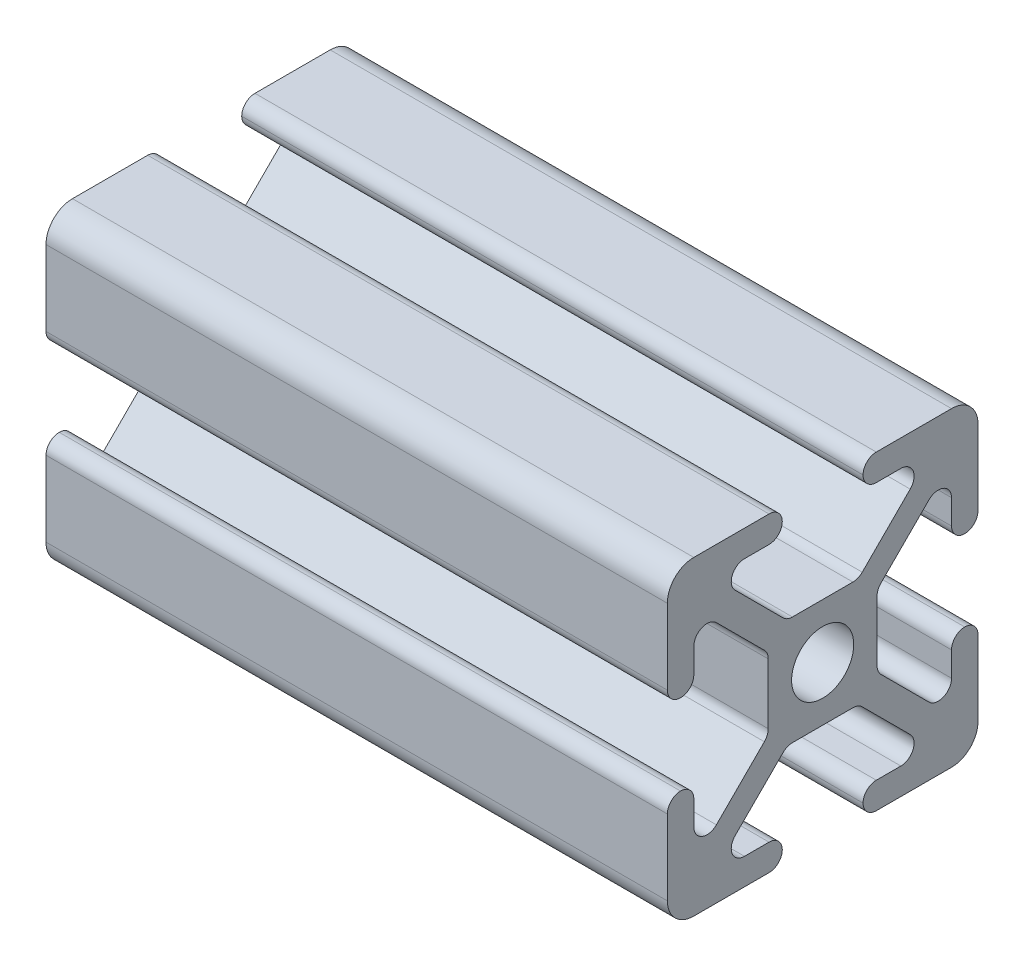
SolidWorks part; units mm, degrees
ref_plane "Front Plane" through (0, 0, 0) normal (1, 0, 0) x (0, 1, 0)
ref_plane "Top Plane" through (0, 0, 0) normal (0, 0, 1) x (0, 1, 0)
ref_plane "Right Plane" through (0, 0, 0) normal (0, 1, 0) x (-1, 0, 0)
sketch "Sketch1" plane through (0, 0, 0) normal (1, 0, 0) x (0, 1, 0)
  line L0 (0, 0) -> (0, 12.5) construction
  line L1 (-12.5, -12.5) -> (12.5, -12.5)
  line L2 (-12.5, -12.5) -> (-12.5, 12.5)
  line L3 (-12.5, 12.5) -> (12.5, 12.5)
  line L4 (12.5, -12.5) -> (12.5, 12.5)
  line L5 (-12.5, -12.5) -> (12.5, 12.5) construction
  line L6 (-12.5, 12.5) -> (12.5, -12.5) construction
  line L7 (-3.25, 12.5) -> (-3.25, 10.37)
  line L8 (-3.25, 10.37) -> (-8.8639, 10.37)
  line L9 (-8.8639, 10.37) -> (-2.8739, 4.38)
  line L10 (-2.8739, 4.38) -> (2.8739, 4.38)
  line L11 (8.8639, 10.37) -> (2.8739, 4.38)
  line L12 (3.25, 10.37) -> (8.8639, 10.37)
  line L13 (3.25, 12.5) -> (3.25, 10.37)
  line L14 (12.5, -3.25) -> (10.37, -3.25)
  line L15 (10.37, -3.25) -> (10.37, -8.8639)
  line L16 (10.37, -8.8639) -> (4.38, -2.8739)
  line L17 (4.38, 2.8739) -> (4.38, -2.8739)
  line L18 (10.37, 8.8639) -> (4.38, 2.8739)
  line L19 (10.37, 3.25) -> (10.37, 8.8639)
  line L20 (12.5, 3.25) -> (10.37, 3.25)
  line L21 (-3.25, -12.5) -> (-3.25, -10.37)
  line L22 (-3.25, -10.37) -> (-8.8639, -10.37)
  line L23 (-8.8639, -10.37) -> (-2.8739, -4.38)
  line L24 (2.8739, -4.38) -> (-2.8739, -4.38)
  line L25 (8.8639, -10.37) -> (2.8739, -4.38)
  line L26 (3.25, -10.37) -> (8.8639, -10.37)
  line L27 (3.25, -12.5) -> (3.25, -10.37)
  line L28 (-12.5, 3.25) -> (-10.37, 3.25)
  line L29 (-10.37, 3.25) -> (-10.37, 8.8639)
  line L30 (-10.37, 8.8639) -> (-4.38, 2.8739)
  line L31 (-4.38, -2.8739) -> (-4.38, 2.8739)
  line L32 (-10.37, -8.8639) -> (-4.38, -2.8739)
  line L33 (-10.37, -3.25) -> (-10.37, -8.8639)
  line L34 (-12.5, -3.25) -> (-10.37, -3.25)
  circle A0 centre (0, 0) radius 2.5
  point P0 (0, 0)
  point P15 (0, 4.38)
  dimension "D3" = 5
  dimension "D1" = 25
  dimension "D2" = 25
  dimension "D4" = 2.13
  dimension "D5" = 2.13
  dimension "D6" = 6.5
  dimension "D7" = 4.38
  dimension "D8" = 4
extrude "Boss-Extrude1" add sketch "Sketch1" along normal blind 50 contours L34 L2 L1 L21 L22 L23 L24 L25 L26 L27 L4 L14 L15 L16 L17 L18 L19 L20 L3 L13 L12 L11 L10 L9 L8 L7 L28 L29 L30 L31 L32 L33 A0 region at (0, -12.1464, -7.875)
fillet "Fillet1" radius 1.065 32 edges at (25, -10.37, -8.8639) (25, 2.8739, -4.38) (25, -2.8739, -4.38) (25, -4.38, 2.8739) (25, -4.38, -2.8739) (25, -2.8739, 4.38) (25, 2.8739, 4.38) (25, 4.38, 2.8739) (25, 4.38, -2.8739) (25, -8.8639, -10.37) (25, 8.8639, -10.37) (25, 10.37, -8.8639) (25, -10.37, 8.8639) (25, -8.8639, 10.37) (25, 10.37, 8.8639) (25, 8.8639, 10.37) (25, 12.5, 3.25) (25, -3.25, -12.5) (25, -10.37, 3.25) (25, 10.37, 3.25) (25, -10.37, -3.25) (25, -12.5, -3.25) (25, -12.5, 3.25) (25, 3.25, -10.37) (25, -3.25, -10.37) (25, 3.25, -12.5) (25, 10.37, -3.25) (25, 12.5, -3.25) (25, 3.25, 12.5) (25, 3.25, 10.37) (25, -3.25, 10.37) (25, -3.25, 12.5)
fillet "Fillet2" radius 2.13 4 edges at (25, 12.5, -12.5) (25, -12.5, -12.5) (25, 12.5, 12.5) (25, -12.5, 12.5)
sketch "Sketch2" plane through (50, 0, 0) normal (1, 0, 0) x (0, 1, 0)
  line L0 (10.37, -12.5) -> (4.315, -12.5)
  line L1 (10.37, -12.5) -> (4.315, -12.5)
  line L2 (4.315, -10.37) -> (6.2927, -10.37)
  line L3 (4.315, -10.37) -> (6.2927, -10.37)
  line L4 (7.0458, -8.5519) -> (3.1858, -4.6919)
  line L5 (7.0458, -8.5519) -> (3.1858, -4.6919)
  line L6 (2.4327, -4.38) -> (-2.4327, -4.38)
  line L7 (2.4327, -4.38) -> (-2.4327, -4.38)
  line L8 (-3.1858, -4.6919) -> (-7.0458, -8.5519)
  line L9 (-3.1858, -4.6919) -> (-7.0458, -8.5519)
  line L10 (-6.2927, -10.37) -> (-4.315, -10.37)
  line L11 (-6.2927, -10.37) -> (-4.315, -10.37)
  line L12 (-4.315, -12.5) -> (-10.37, -12.5)
  line L13 (-4.315, -12.5) -> (-10.37, -12.5)
  line L14 (-12.5, -10.37) -> (-12.5, -4.315)
  line L15 (-12.5, -10.37) -> (-12.5, -4.315)
  line L16 (-10.37, -4.315) -> (-10.37, -6.2927)
  line L17 (-10.37, -4.315) -> (-10.37, -6.2927)
  line L18 (-8.5519, -7.0458) -> (-4.6919, -3.1858)
  line L19 (-8.5519, -7.0458) -> (-4.6919, -3.1858)
  line L20 (-4.38, -2.4327) -> (-4.38, 2.4327)
  line L21 (-4.38, -2.4327) -> (-4.38, 2.4327)
  line L22 (-4.6919, 3.1858) -> (-8.5519, 7.0458)
  line L23 (-4.6919, 3.1858) -> (-8.5519, 7.0458)
  line L24 (-10.37, 6.2927) -> (-10.37, 4.315)
  line L25 (-10.37, 6.2927) -> (-10.37, 4.315)
  line L26 (-12.5, 4.315) -> (-12.5, 10.37)
  line L27 (-12.5, 4.315) -> (-12.5, 10.37)
  line L28 (-10.37, 12.5) -> (-4.315, 12.5)
  line L29 (-10.37, 12.5) -> (-4.315, 12.5)
  line L30 (-4.315, 10.37) -> (-6.2927, 10.37)
  line L31 (-4.315, 10.37) -> (-6.2927, 10.37)
  line L32 (-7.0458, 8.5519) -> (-3.1858, 4.6919)
  line L33 (-7.0458, 8.5519) -> (-3.1858, 4.6919)
  line L34 (-2.4327, 4.38) -> (2.4327, 4.38)
  line L35 (-2.4327, 4.38) -> (2.4327, 4.38)
  line L36 (3.1858, 4.6919) -> (7.0458, 8.5519)
  line L37 (3.1858, 4.6919) -> (7.0458, 8.5519)
  line L38 (6.2927, 10.37) -> (4.315, 10.37)
  line L39 (6.2927, 10.37) -> (4.315, 10.37)
  line L40 (4.315, 12.5) -> (10.37, 12.5)
  line L41 (4.315, 12.5) -> (10.37, 12.5)
  line L42 (12.5, 10.37) -> (12.5, 4.315)
  line L43 (12.5, 10.37) -> (12.5, 4.315)
  line L44 (10.37, 4.315) -> (10.37, 6.2927)
  line L45 (10.37, 4.315) -> (10.37, 6.2927)
  line L46 (8.5519, 7.0458) -> (4.6919, 3.1858)
  line L47 (8.5519, 7.0458) -> (4.6919, 3.1858)
  line L48 (4.38, 2.4327) -> (4.38, -2.4327)
  line L49 (4.38, 2.4327) -> (4.38, -2.4327)
  line L50 (4.6919, -3.1858) -> (8.5519, -7.0458)
  line L51 (4.6919, -3.1858) -> (8.5519, -7.0458)
  line L52 (10.37, -6.2927) -> (10.37, -4.315)
  line L53 (10.37, -6.2927) -> (10.37, -4.315)
  line L54 (12.5, -4.315) -> (12.5, -10.37)
  line L55 (12.5, -4.315) -> (12.5, -10.37)
  arc A0 (10.37, -12.5) -> (12.5, -10.37) centre (10.37, -10.37) ccw
  circle A1 centre (0, 0) radius 2.5
  circle A2 centre (0, 0) radius 2.5
  arc A3 (10.37, -12.5) -> (12.5, -10.37) centre (10.37, -10.37) ccw
  arc A4 (3.25, -11.435) -> (4.315, -12.5) centre (4.315, -11.435) ccw
  arc A5 (3.25, -11.435) -> (4.315, -12.5) centre (4.315, -11.435) ccw
  arc A6 (4.315, -10.37) -> (3.25, -11.435) centre (4.315, -11.435) ccw
  arc A7 (4.315, -10.37) -> (3.25, -11.435) centre (4.315, -11.435) ccw
  arc A8 (6.2927, -10.37) -> (7.0458, -8.5519) centre (6.2927, -9.305) ccw
  arc A9 (6.2927, -10.37) -> (7.0458, -8.5519) centre (6.2927, -9.305) ccw
  arc A10 (3.1858, -4.6919) -> (2.4327, -4.38) centre (2.4327, -5.445) ccw
  arc A11 (3.1858, -4.6919) -> (2.4327, -4.38) centre (2.4327, -5.445) ccw
  arc A12 (-2.4327, -4.38) -> (-3.1858, -4.6919) centre (-2.4327, -5.445) ccw
  arc A13 (-2.4327, -4.38) -> (-3.1858, -4.6919) centre (-2.4327, -5.445) ccw
  arc A14 (-7.0458, -8.5519) -> (-6.2927, -10.37) centre (-6.2927, -9.305) ccw
  arc A15 (-7.0458, -8.5519) -> (-6.2927, -10.37) centre (-6.2927, -9.305) ccw
  arc A16 (-3.25, -11.435) -> (-4.315, -10.37) centre (-4.315, -11.435) ccw
  arc A17 (-3.25, -11.435) -> (-4.315, -10.37) centre (-4.315, -11.435) ccw
  arc A18 (-4.315, -12.5) -> (-3.25, -11.435) centre (-4.315, -11.435) ccw
  arc A19 (-4.315, -12.5) -> (-3.25, -11.435) centre (-4.315, -11.435) ccw
  arc A20 (-12.5, -10.37) -> (-10.37, -12.5) centre (-10.37, -10.37) ccw
  arc A21 (-12.5, -10.37) -> (-10.37, -12.5) centre (-10.37, -10.37) ccw
  arc A22 (-11.435, -3.25) -> (-12.5, -4.315) centre (-11.435, -4.315) ccw
  arc A23 (-11.435, -3.25) -> (-12.5, -4.315) centre (-11.435, -4.315) ccw
  arc A24 (-10.37, -4.315) -> (-11.435, -3.25) centre (-11.435, -4.315) ccw
  arc A25 (-10.37, -4.315) -> (-11.435, -3.25) centre (-11.435, -4.315) ccw
  arc A26 (-10.37, -6.2927) -> (-8.5519, -7.0458) centre (-9.305, -6.2927) ccw
  arc A27 (-10.37, -6.2927) -> (-8.5519, -7.0458) centre (-9.305, -6.2927) ccw
  arc A28 (-4.6919, -3.1858) -> (-4.38, -2.4327) centre (-5.445, -2.4327) ccw
  arc A29 (-4.6919, -3.1858) -> (-4.38, -2.4327) centre (-5.445, -2.4327) ccw
  arc A30 (-4.38, 2.4327) -> (-4.6919, 3.1858) centre (-5.445, 2.4327) ccw
  arc A31 (-4.38, 2.4327) -> (-4.6919, 3.1858) centre (-5.445, 2.4327) ccw
  arc A32 (-8.5519, 7.0458) -> (-10.37, 6.2927) centre (-9.305, 6.2927) ccw
  arc A33 (-8.5519, 7.0458) -> (-10.37, 6.2927) centre (-9.305, 6.2927) ccw
  arc A34 (-11.435, 3.25) -> (-10.37, 4.315) centre (-11.435, 4.315) ccw
  arc A35 (-11.435, 3.25) -> (-10.37, 4.315) centre (-11.435, 4.315) ccw
  arc A36 (-12.5, 4.315) -> (-11.435, 3.25) centre (-11.435, 4.315) ccw
  arc A37 (-12.5, 4.315) -> (-11.435, 3.25) centre (-11.435, 4.315) ccw
  arc A38 (-10.37, 12.5) -> (-12.5, 10.37) centre (-10.37, 10.37) ccw
  arc A39 (-10.37, 12.5) -> (-12.5, 10.37) centre (-10.37, 10.37) ccw
  arc A40 (-3.25, 11.435) -> (-4.315, 12.5) centre (-4.315, 11.435) ccw
  arc A41 (-3.25, 11.435) -> (-4.315, 12.5) centre (-4.315, 11.435) ccw
  arc A42 (-4.315, 10.37) -> (-3.25, 11.435) centre (-4.315, 11.435) ccw
  arc A43 (-4.315, 10.37) -> (-3.25, 11.435) centre (-4.315, 11.435) ccw
  arc A44 (-6.2927, 10.37) -> (-7.0458, 8.5519) centre (-6.2927, 9.305) ccw
  arc A45 (-6.2927, 10.37) -> (-7.0458, 8.5519) centre (-6.2927, 9.305) ccw
  arc A46 (-3.1858, 4.6919) -> (-2.4327, 4.38) centre (-2.4327, 5.445) ccw
  arc A47 (-3.1858, 4.6919) -> (-2.4327, 4.38) centre (-2.4327, 5.445) ccw
  arc A48 (2.4327, 4.38) -> (3.1858, 4.6919) centre (2.4327, 5.445) ccw
  arc A49 (2.4327, 4.38) -> (3.1858, 4.6919) centre (2.4327, 5.445) ccw
  arc A50 (7.0458, 8.5519) -> (6.2927, 10.37) centre (6.2927, 9.305) ccw
  arc A51 (7.0458, 8.5519) -> (6.2927, 10.37) centre (6.2927, 9.305) ccw
  arc A52 (3.25, 11.435) -> (4.315, 10.37) centre (4.315, 11.435) ccw
  arc A53 (3.25, 11.435) -> (4.315, 10.37) centre (4.315, 11.435) ccw
  arc A54 (4.315, 12.5) -> (3.25, 11.435) centre (4.315, 11.435) ccw
  arc A55 (4.315, 12.5) -> (3.25, 11.435) centre (4.315, 11.435) ccw
  arc A56 (12.5, 10.37) -> (10.37, 12.5) centre (10.37, 10.37) ccw
  arc A57 (12.5, 10.37) -> (10.37, 12.5) centre (10.37, 10.37) ccw
  arc A58 (11.435, 3.25) -> (12.5, 4.315) centre (11.435, 4.315) ccw
  arc A59 (11.435, 3.25) -> (12.5, 4.315) centre (11.435, 4.315) ccw
  arc A60 (10.37, 4.315) -> (11.435, 3.25) centre (11.435, 4.315) ccw
  arc A61 (10.37, 4.315) -> (11.435, 3.25) centre (11.435, 4.315) ccw
  arc A62 (10.37, 6.2927) -> (8.5519, 7.0458) centre (9.305, 6.2927) ccw
  arc A63 (10.37, 6.2927) -> (8.5519, 7.0458) centre (9.305, 6.2927) ccw
  arc A64 (4.6919, 3.1858) -> (4.38, 2.4327) centre (5.445, 2.4327) ccw
  arc A65 (4.6919, 3.1858) -> (4.38, 2.4327) centre (5.445, 2.4327) ccw
  arc A66 (4.38, -2.4327) -> (4.6919, -3.1858) centre (5.445, -2.4327) ccw
  arc A67 (4.38, -2.4327) -> (4.6919, -3.1858) centre (5.445, -2.4327) ccw
  arc A68 (8.5519, -7.0458) -> (10.37, -6.2927) centre (9.305, -6.2927) ccw
  arc A69 (8.5519, -7.0458) -> (10.37, -6.2927) centre (9.305, -6.2927) ccw
  arc A70 (11.435, -3.25) -> (10.37, -4.315) centre (11.435, -4.315) ccw
  arc A71 (11.435, -3.25) -> (10.37, -4.315) centre (11.435, -4.315) ccw
  arc A72 (12.5, -4.315) -> (11.435, -3.25) centre (11.435, -4.315) ccw
  arc A73 (12.5, -4.315) -> (11.435, -3.25) centre (11.435, -4.315) ccw
  dimension "D1" = 0
